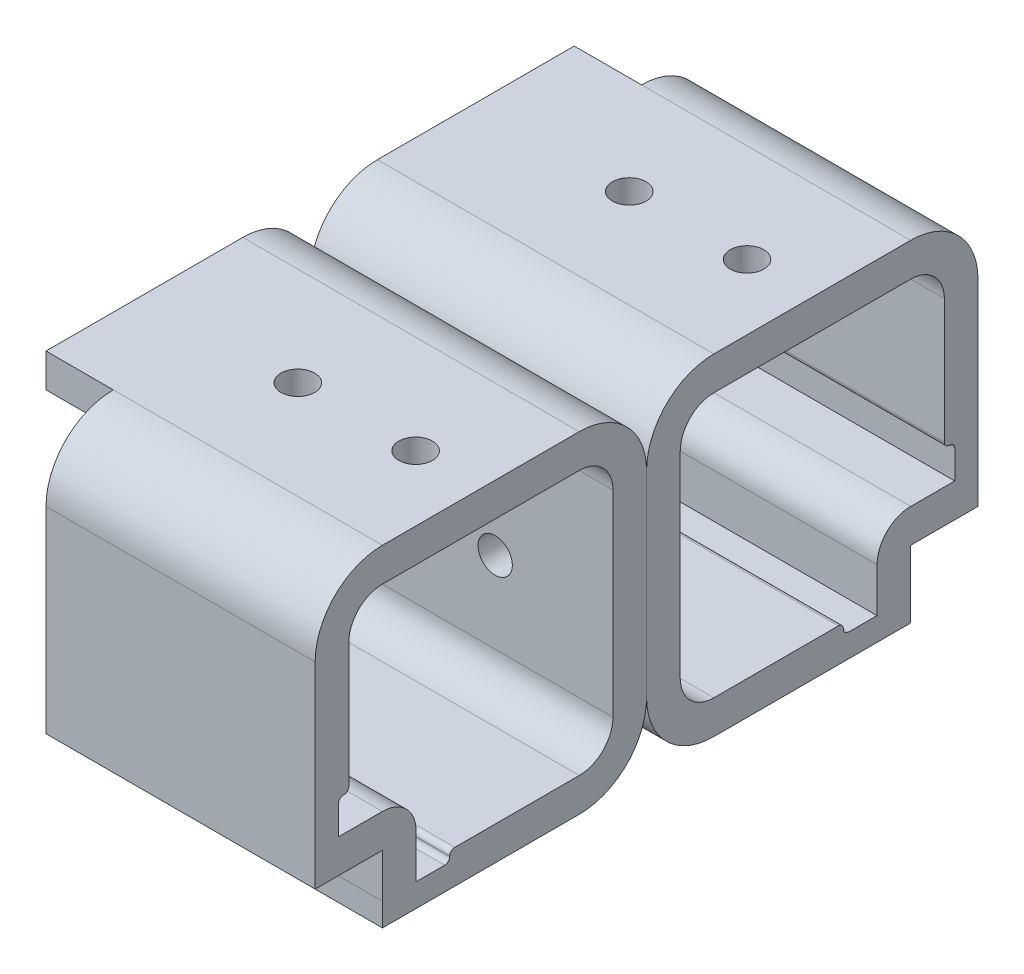
SolidWorks part; units mm, degrees
other "Markup1"
sketch "Sketch9" plane through (-30, -44.15, 149.3074) normal (-0.1426, -0.0355, 0.9891) x (-0.1076, 0.994, 0.0202)
material "ABS"
ref_plane "Front Plane" through (0, 0, 0) normal (0, 0, 1) x (1, 0, 0)
ref_plane "Top Plane" through (0, 0, 0) normal (0, 1, 0) x (1, 0, 0)
ref_plane "Right Plane" through (0, 0, 0) normal (1, 0, 0) x (0, 0, -1)
sketch "Sketch2" plane through (0, 0, 0) normal (1, 0, 0) x (0, 0, -1)
  line L0 (-40.8, -13.55) -> (-40.8, -17.45) construction
  line L1 (27.7074, 44.3574) -> (-30.8, 44.3574)
  line L2 (37.7074, 34.3574) -> (37.7074, -24.15)
  line L3 (27.7074, -34.15) -> (-30.8, -34.15)
  line L4 (-40.8, 34.3574) -> (-40.8, -24.15)
  line L5 (-50.8, 15) -> (-40.8, 15) construction
  line L10 (-48.05, 15) -> (-59.05, 15) construction
  line L11 (-50.8, -15) -> (-40.8, -15) construction
  line L12 (-59.05, -15) -> (-48.05, -15) construction
  line L13 (27.7074, 54.3574) -> (-30.8, 54.3574)
  line L14 (-50.8, 34.3574) -> (-50.8, -24.15)
  line L15 (27.7074, -44.15) -> (-30.8, -44.15)
  line L16 (47.7074, 34.3574) -> (47.7074, -24.15)
  line L18 (642.3574, 34.3574) -> (642.3574, -24.15) construction
  line L19 (-40.05, -21.15) -> (-29.05, -21.15) construction
  arc A0 (-30.8, 44.3574) -> (-40.8, 34.3574) centre (-30.8, 34.3574) ccw
  arc A1 (-30.8, -34.15) -> (-40.8, -24.15) centre (-30.8, -24.15) cw
  arc A2 (27.7074, -34.15) -> (37.7074, -24.15) centre (27.7074, -24.15) ccw
  arc A3 (27.7074, 44.3574) -> (37.7074, 34.3574) centre (27.7074, 34.3574) cw
  arc A4 (-30.8, 54.3574) -> (-50.8, 34.3574) centre (-30.8, 34.3574) ccw
  arc A5 (-30.8, -44.15) -> (-50.8, -24.15) centre (-30.8, -24.15) cw
  arc A6 (27.7074, -44.15) -> (47.7074, -24.15) centre (27.7074, -24.15) ccw
  arc A7 (27.7074, 54.3574) -> (47.7074, 34.3574) centre (27.7074, 34.3574) cw
  arc A8 (27.7074, 44.3574) -> (37.7074, 34.3574) centre (27.7074, 34.3574) cw construction
  dimension "D1" = 10
  dimension "D2" = 10
  dimension "D3" = 3
extrude "Boss-Extrude1" add sketch "Sketch2" along normal blind 70 and the other way blind 30
sketch "Sketch3" plane through (0, 0, 50.8) normal (0, 0, 1) x (1, 0, 0)
  line L2 (0, 20.85) -> (0, 20.75)
  line L3 (0, 15.75) -> (0, 15.65)
  circle A0 centre (0, 0) radius 5.2
  circle A1 centre (0, 0) radius 4.2 construction
  arc A11 (0, 20.85) -> (0, 15.65) centre (0, 18.25) ccw construction
  circle A12 centre (35, 0) radius 5.1 construction
  circle A13 centre (35, 0) radius 5.1
  arc A14 (0, 15.65) -> (0, 20.85) centre (0, 18.25) ccw
  arc A15 (0, 15.75) -> (0, 20.75) centre (0, 18.25) ccw
  arc A16 (0, 15.65) -> (0, 20.85) centre (0, 18.25) ccw
  arc A18 (0, -15.65) -> (0, -20.85) centre (0, -18.25) ccw construction
  arc A19 (0, -20.85) -> (0, -15.65) centre (0, -18.25) ccw construction
  circle A20 centre (0, 0) radius 4.2 construction
  arc A21 (0, 20.85) -> (0, 15.65) centre (0, 18.25) ccw
  arc A22 (0, -15.65) -> (0, -20.85) centre (0, -18.25) ccw
  arc A23 (0, -20.85) -> (0, -15.65) centre (0, -18.25) ccw
  point P9 (0, 0)
  dimension "D1" = 0
  dimension "D2" = 1
extrude "Cut-Extrude1" cut sketch "Sketch3" against normal up to next
sketch "Sketch4" plane through (0, 54.3574, 0) normal (0, 1, 0) x (1, 0, 0)
  line L0 (50.6, -1.5463) -> (15.6, -1.5463) construction
  line L1 (-30, 27.7074) -> (70, 27.7074) construction
  line L2 (-30, -30.8) -> (70, -30.8) construction
  line L3 (28.05, -14.6463) -> (38.15, -14.6463) construction
  line L4 (28.05, -14.6463) -> (38.15, -14.6463) construction
  line L5 (33.1, -14.6463) -> (33.1, -1.5463) construction
  circle A0 centre (15.6, -1.5463) radius 5
  circle A1 centre (50.6, -1.5463) radius 5
  point P12 (33.1, -1.5463)
  dimension "D1" = 10
  dimension "D2" = 35
extrude "Cut-Extrude2" cut sketch "Sketch4" against normal up to next
sketch "Sketch5" plane through (0, 0, 50.8) normal (0, 0, 1) x (1, 0, 0)
  line L0 (-30, -24.15) -> (70, -24.15) construction
  line L1 (-10, -24.15) -> (-30, -24.15)
  line L2 (-10, -24.15) -> (-10, -44.15)
  line L3 (-10, -44.15) -> (-30, -44.15)
  line L4 (-30, -24.15) -> (-30, -44.15)
  line L5 (-30, 34.3574) -> (-30, -24.15) construction
  line L6 (-30, -44.15) -> (70, -44.15) construction
  dimension "D1" = 20
extrude "Cut-Extrude3" cut sketch "Sketch5" against normal through all both and the other way through all
sketch "Sketch6" plane through (0, 54.3574, 0) normal (0, 1, 0) x (1, 0, 0)
  line L0 (-30, 27.7074) -> (-30, -30.8) construction
  line L1 (-30, 47.7074) -> (-10, 47.7074)
  line L2 (-30, 47.7074) -> (-30, 27.7074)
  line L3 (-30, 27.7074) -> (-10, 27.7074)
  line L4 (-10, 47.7074) -> (-10, 27.7074)
  line L5 (-30, 27.7074) -> (70, 27.7074) construction
  line L6 (-30, 47.7074) -> (70, 47.7074) construction
  dimension "D1" = 20
extrude "Cut-Extrude4" cut sketch "Sketch6" against normal through all
sketch "Sketch7" plane through (-10, 0, 0) normal (-1, 0, 0) x (0, 0, 1)
  line L10 (-27.7074, -44.15) -> (30.8, -44.15) construction
  line L11 (-47.7074, -24.15) -> (-27.7074, -24.15)
  line L12 (-47.7074, -24.15) -> (-47.7074, -44.15)
  line L13 (-47.7074, -44.15) -> (-27.7074, -44.15)
  line L14 (-27.7074, -24.15) -> (-27.7074, -44.15)
  line L15 (-47.7074, -24.15) -> (-47.7074, 34.3574) construction
  line L16 (-37.7074, 34.3574) -> (-37.7074, -24.15) construction
  line L17 (-37.7074, -4.15) -> (-40.8074, -4.15)
  line L18 (-37.7074, -4.15) -> (-37.7074, -24.15)
  line L19 (-37.7074, -24.15) -> (-40.8074, -24.15)
  line L20 (-40.8074, -4.15) -> (-40.8074, -24.15)
  line L21 (-27.7074, -34.15) -> (30.8, -34.15) construction
  line L22 (-27.7074, -37.25) -> (-7.7074, -37.25)
  line L23 (-27.7074, -37.25) -> (-27.7074, -34.15)
  line L24 (-27.7074, -34.15) -> (-7.7074, -34.15)
  line L25 (-7.7074, -37.25) -> (-7.7074, -34.15)
  line L26 (-40.8074, -24.7292) -> (-40.8074, -25.6692) construction
  arc M8 (-27.7074, -34.15) -> (-37.7074, -24.15) centre (-27.7074, -24.15) cw
  arc M14 (-47.7074, -24.15) -> (-27.7074, -44.15) centre (-27.7074, -24.15) ccw
  dimension "D1" = 20
  dimension "D2" = 20
extrude "Cut-Extrude5" cut sketch "Sketch7" against normal through all contours L14 L11 M8 M14 | L18 L17 L20 L19 | L23 L22 L25 L24 region at (-10, -34.053, -37.6104)
sketch "Sketch8" plane through (-10, 0, 0) normal (-1, 0, 0) x (0, 0, 1)
  line L0 (-47.7074, -14.1507) -> (-27.7066, -14.1507)
  line L1 (-47.7074, -24.15) -> (-47.7074, 34.3574) construction
  line L2 (-17.7066, -24.1507) -> (-17.7066, -44.15)
  line L3 (-27.7074, -44.15) -> (30.8, -44.15) construction
  line L4 (-47.7074, -24.1507) -> (-27.7066, -24.1507)
  line L5 (-27.7066, -24.1507) -> (-27.7066, -44.15)
  line L6 (-29.2066, -24.1507) -> (-33.8266, -24.1507) construction
  line L7 (-27.7066, -25.6507) -> (-27.7066, -30.2707) construction
  line L8 (-47.7074, -14.1507) -> (-47.7074, -24.1507)
  line L9 (-27.7066, -44.15) -> (-17.7066, -44.15)
  line L10 (-17.7066, -14.1507) -> (-17.7066, -44.15) construction
  line L11 (-47.7074, -14.1507) -> (-17.7066, -14.1507) construction
  arc A0 (-17.7066, -24.1507) -> (-27.7066, -14.1507) centre (-27.7066, -24.1507) ccw
  dimension "D2" = 10
  dimension "D1" = 10
extrude "Boss-Extrude2" add sketch "Sketch8" against normal up to surface (80 mm away) up to face at (70, 0.2536, -3.3038)
fillet "Fillet1" radius 1.5 4 edges at (30, -37.25, -7.7074) (30, -4.15, -40.8074) (30, -34.15, -7.7074) (30, -4.15, -37.7074)
mirror "Mirror1" about plane through (-30, 34.3574, 50.8) normal (0, 0, 1) of bodies 108
